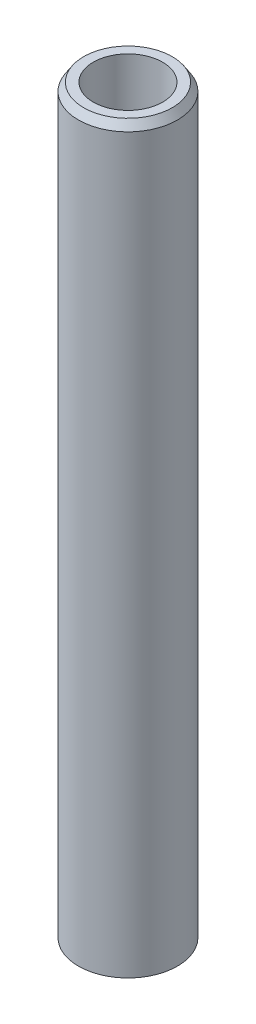
SolidWorks part; units mm, degrees
ref_plane "Front Plane" through (0, 0, 0) normal (0, 0, 1) x (1, 0, 0)
ref_plane "Top Plane" through (0, 0, 0) normal (0, 1, 0) x (1, 0, 0)
ref_plane "Right Plane" through (0, 0, 0) normal (1, 0, 0) x (0, 0, -1)
sketch "Sketch1" plane through (0, 0, 0) normal (0, 1, 0) x (1, 0, 0)
  circle A0 centre (0, 0) radius 25
  dimension "SHAFT_OD" = 50
extrude "Boss-Extrude1" add sketch "Sketch1" along normal blind 376.8886
sketch "Sketch2" plane through (0, 0, 0) normal (0, 1, 0) x (1, 0, 0)
  circle A0 centre (0, 0) radius 17.5172
  dimension "BORE_D" = 35.0343
extrude "Cut-Extrude1" cut sketch "Sketch2" along normal through all
chamfer "Chamfer1" distance 4.072 angle 32.867 2 edges at (0, 376.8886, 25) (0, 0, 25) first distance on face at (0, 376.8886, 25) first distance on face at (0, 0, 17.5172)
